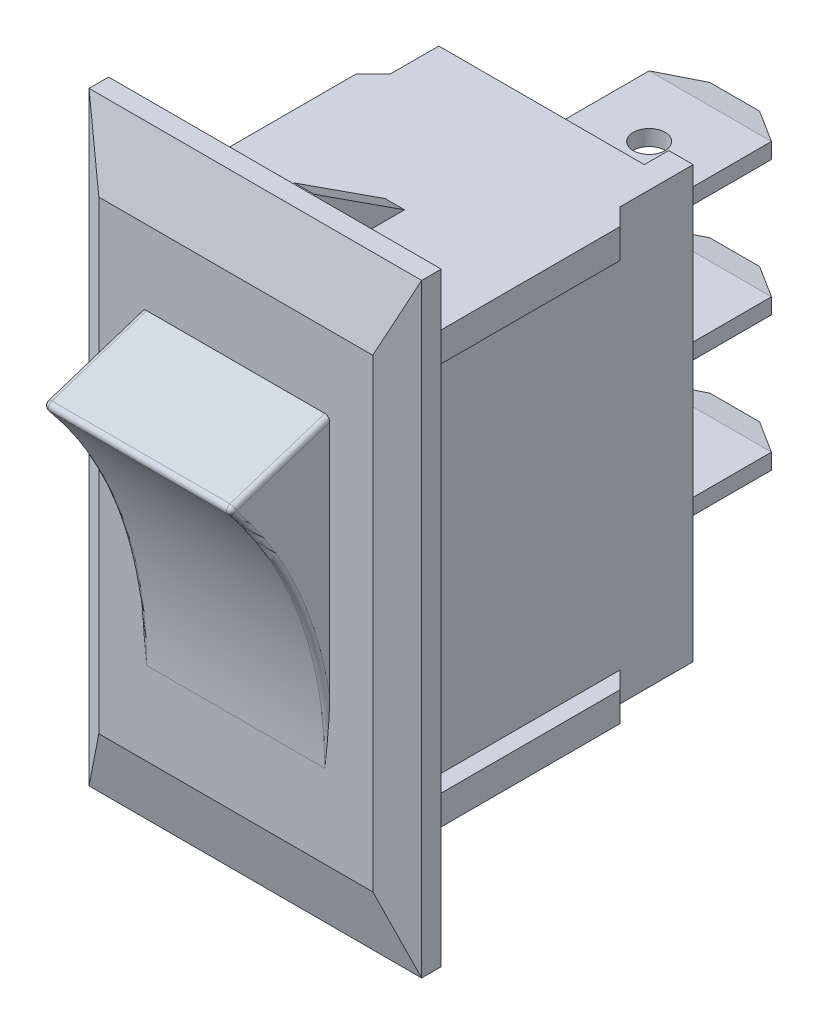
SolidWorks part; units mm, degrees
ref_plane "Front Plane" through (0, 0, 0) normal (0, 0, 1) x (1, 0, 0)
ref_plane "Top Plane" through (0, 0, 0) normal (0, 1, 0) x (1, 0, 0)
ref_plane "Right Plane" through (0, 0, 0) normal (1, 0, 0) x (0, 0, -1)
sketch "Sketch1" plane through (0, 0, 0) normal (0, 0, 1) x (1, 0, 0)
  line L0 (-5.969, -11.176) -> (5.969, 11.176) construction
  line L1 (-5.969, 11.176) -> (5.969, 11.176)
  line L2 (-5.969, 11.176) -> (-5.969, -11.176)
  line L3 (-5.969, -11.176) -> (5.969, -11.176)
  line L4 (5.969, 11.176) -> (5.969, -11.176)
  point P4 (0, 0)
  dimension "D1" = 11.938
  dimension "D2" = 22.352
extrude "Boss-Extrude1" add sketch "Sketch1" against normal blind 14.478
sketch "Sketch2" plane through (0, 0, 0) normal (0, 0, 1) x (1, 0, 0)
  line L0 (-8.636, -15.6845) -> (8.636, 15.6845) construction
  line L1 (-8.636, 15.6845) -> (8.636, 15.6845)
  line L2 (-8.636, 15.6845) -> (-8.636, -15.6845)
  line L3 (-8.636, -15.6845) -> (8.636, -15.6845)
  line L4 (8.636, 15.6845) -> (8.636, -15.6845)
  point P4 (0, 0)
  dimension "D1" = 31.369
  dimension "D2" = 17.272
extrude "Boss-Extrude2" add sketch "Sketch2" along normal blind 2.032
sketch "Sketch3" plane through (0, 0, -14.478) normal (0, 0, -1) x (-1, 0, 0)
  line L0 (5.969, -11.176) -> (-5.969, -11.176) construction
  line L1 (-5.969, 11.176) -> (-4.699, 11.176)
  line L2 (-5.969, 11.176) -> (-5.969, -11.176)
  line L3 (-5.969, -11.176) -> (-4.699, -11.176)
  line L4 (-4.699, 11.176) -> (-4.699, -11.176)
  dimension "D1" = 1.27
extrude "Boss-Extrude3" add sketch "Sketch3" along normal blind 1.27
sketch "Sketch4" plane through (8.636, 0, 0) normal (1, 0, 0) x (0, 0, -1)
  line L0 (-1.016, 15.6845) -> (-2.032, 12.065)
  line L1 (-2.032, 15.6845) -> (0, 15.6845) construction
  line L2 (-2.032, -15.6845) -> (-2.032, 15.6845) construction
  line L3 (-2.032, 12.065) -> (-2.032, 15.6845)
  line L4 (-2.032, 15.6845) -> (-1.016, 15.6845)
  line L5 (-2.032, 0) -> (0, 0) construction
  line L6 (-2.032, -12.065) -> (-2.032, -15.6845)
  line L7 (-2.032, -15.6845) -> (-1.016, -15.6845)
  line L8 (-1.016, -15.6845) -> (-2.032, -12.065)
  line L9 (0, -15.6845) -> (0, 15.6845) construction
  dimension "D1" = 24.13
  dimension "D2" = 1.016
extrude "Cut-Extrude1" cut sketch "Sketch4" against normal through all
sketch "Sketch5" plane through (0, 15.6845, 0) normal (0, 1, 0) x (1, 0, 0)
  line L0 (0, 0) -> (0, -2.032) construction
  line L1 (-8.636, -2.032) -> (8.636, -2.032) construction
  line L2 (-8.636, -1.016) -> (-8.636, -2.032)
  line L3 (-8.636, -2.032) -> (-7.112, -2.032)
  line L4 (-7.112, -2.032) -> (-8.636, -1.016)
  line L5 (8.636, -2.032) -> (7.112, -2.032)
  line L6 (8.636, -1.016) -> (8.636, -2.032)
  line L7 (7.112, -2.032) -> (8.636, -1.016)
  dimension "D1" = 14.224
extrude "Cut-Extrude2" cut sketch "Sketch5" against normal through all
sketch "Sketch9" plane through (0, 11.176, 0) normal (0, 1, 0) x (1, 0, 0)
  line L0 (5.969, 0) -> (-5.969, 0) construction
  line L1 (-0.508, 0) -> (0.508, 0)
  line L2 (-0.508, 0) -> (-0.508, 6.223)
  line L3 (-0.508, 6.223) -> (0.508, 6.223)
  line L4 (0.508, 0) -> (0.508, 6.223)
  line L5 (8.636, 0) -> (-8.636, 0) construction
  point P6 (0, 0)
  dimension "D1" = 6.223
  dimension "D2" = 1.016
extrude "Boss-Extrude5" add sketch "Sketch9" along normal blind 3.048
sketch "Sketch10" plane through (0.508, 0, 0) normal (1, 0, 0) x (0, 0, -1)
  line L0 (6.223, 11.176) -> (1.524, 14.224)
  line L1 (0, 14.224) -> (6.223, 14.224) construction
  line L2 (1.524, 14.224) -> (6.223, 14.224)
  line L3 (6.223, 14.224) -> (6.223, 11.176)
  line L4 (0, -15.6845) -> (0, 15.6845) construction
  dimension "D1" = 1.524
extrude "Cut-Extrude5" cut sketch "Sketch10" against normal through all
mirror "Mirror1" about plane through (0, 0, 0) normal (0, 1, 0) of "Cut-Extrude5", "Boss-Extrude5"
sketch "Sketch11" plane through (5.969, 0, 0) normal (1, 0, 0) x (0, 0, -1)
  line L0 (15.748, 0) -> (0, 0) construction
  line L1 (0, 11.176) -> (11.938, 11.176)
  line L2 (0, 11.176) -> (0, 9.652)
  line L3 (0, 9.652) -> (11.938, 9.652)
  line L4 (11.938, 11.176) -> (11.938, 9.652)
  line L5 (15.748, 11.176) -> (15.748, -11.176) construction
  line L6 (0, -9.652) -> (11.938, -9.652)
  line L7 (11.938, -11.176) -> (11.938, -9.652)
  line L8 (0, -11.176) -> (11.938, -11.176)
  line L9 (0, -11.176) -> (0, -9.652)
  dimension "D1" = 1.524
  dimension "D2" = 11.938
extrude "Boss-Extrude6" add sketch "Sketch11" along normal blind 0.889
sketch "Sketch12" plane through (0, 11.176, 0) normal (0, 1, 0) x (1, 0, 0)
  line L0 (5.969, 11.938) -> (6.858, 11.938)
  line L1 (6.858, 11.938) -> (6.858, 11.049)
  line L2 (6.858, 11.938) -> (6.858, 0) construction
  line L3 (6.858, 11.049) -> (5.969, 11.938)
  dimension "D1" = 45
extrude "Cut-Extrude6" cut sketch "Sketch12" against normal through all
mirror "Mirror2" about plane through (0, 0, 0) normal (1, 0, 0) of "Cut-Extrude6", "Boss-Extrude6"
ref_plane "Plane1" through (4.8768, 0, 0) normal (1, 0, 0) x (0, 0, -1)
sketch "Sketch13" plane through (4.8768, 0, 0) normal (1, 0, 0) x (0, 0, -1)
  line L0 (-2.032, -12.065) -> (-2.032, 12.065) construction
  line L1 (0, -15.6845) -> (0, 15.6845) construction
  line L2 (15.748, 0) -> (-22.7267, 0) construction
  line L3 (15.748, 11.176) -> (15.748, -11.176) construction
  line L4 (0, 0) -> (-22.711, 7.3792) construction
  line L5 (0, 0) -> (-23.8664, -7.7547) construction
  line L6 (-7.3152, 6.4861) -> (-2.032, 8.2027)
  line L7 (-2.032, 8.2027) -> (-2.032, -7.7547)
  arc A0 (-2.032, -7.7547) -> (-7.3152, 6.4861) centre (-23.8664, -7.7547) ccw
  dimension "D1" = 7.3152
  dimension "D2" = 18
  dimension "D3" = 18
  dimension "D4" = 8.4292
extrude "Boss-Extrude7" add sketch "Sketch13" against normal blind 9.7536
fillet "Fillet2" radius 0.254 5 edges at (-4.8768, -0.1601, 3.3954) (4.8768, -0.1601, 3.3954) (-4.8768, 7.3444, 4.6736) (0, 6.4861, 7.3152) (4.8768, 7.3444, 4.6736)
sketch "Sketch6" plane through (0, 0, -14.478) normal (0, 0, -1) x (-1, 0, 0)
  line L0 (-3.175, -0.4064) -> (3.175, 0.4064) construction
  line L1 (-3.175, 0.4064) -> (3.175, 0.4064)
  line L2 (-3.175, 0.4064) -> (-3.175, -0.4064)
  line L3 (-3.175, -0.4064) -> (3.175, -0.4064)
  line L4 (3.175, 0.4064) -> (3.175, -0.4064)
  point P4 (0, 0)
  dimension "D1" = 6.35
  dimension "D2" = 0.8128
extrude "Boss-Extrude4" add sketch "Sketch6" along normal blind 9.398
chamfer "Chamfer1" distance 1.27 angle 56 2 edges at (-3.175, 0, -23.876) (3.175, 0, -23.876)
sketch "Sketch7" plane through (3.175, 0, 0) normal (1, 0, 0) x (0, 0, -1)
  line L0 (22.606, 0.4064) -> (23.876, 0.1905)
  line L1 (23.876, 0.4064) -> (23.876, -0.4064) construction
  line L2 (23.876, 0.1905) -> (23.876, 0.4064)
  line L3 (23.876, 0.4064) -> (22.606, 0.4064)
  line L4 (23.876, 0) -> (22.606, 0) construction
  line L5 (22.606, -0.4064) -> (22.606, 0.4064) construction
  line L6 (23.876, -0.1905) -> (23.876, -0.4064)
  line L7 (23.876, -0.4064) -> (22.606, -0.4064)
  line L8 (22.606, -0.4064) -> (23.876, -0.1905)
  dimension "D1" = 0.381
extrude "Cut-Extrude3" cut sketch "Sketch7" against normal through all
sketch "Sketch8" plane through (0, 0.4064, 0) normal (0, 1, 0) x (1, 0, 0)
  line L0 (0, 23.876) -> (0, 14.478) construction
  line L1 (-1.2921, 23.876) -> (1.2921, 23.876) construction
  line L2 (-3.175, 14.478) -> (3.175, 14.478) construction
  circle A0 centre (0, 19.431) radius 0.8255
  dimension "D1" = 1.651
  dimension "D2" = 4.445
extrude "Cut-Extrude4" cut sketch "Sketch8" against normal through all
pattern_linear "LPattern1" count 2 spacing 6.985 along (0, 1, 0) count 2 spacing 6.985 along (0, -1, 0) of "Boss-Extrude4", "Chamfer1", "Cut-Extrude3", "Cut-Extrude4"
